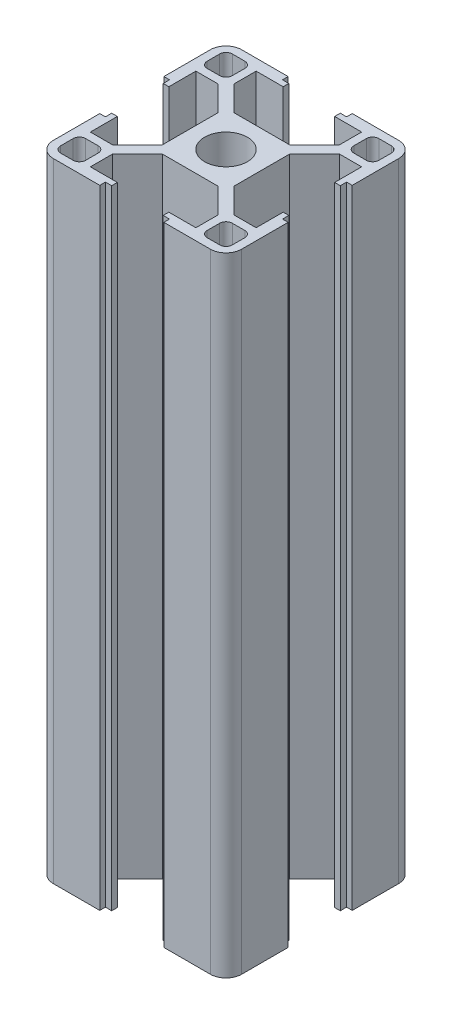
SolidWorks part; units mm, degrees
ref_plane "Front Plane" through (0, 0, 0) normal (0, 0, 1) x (1, 0, 0)
ref_plane "Top Plane" through (0, 0, 0) normal (0, 1, 0) x (1, 0, 0)
ref_plane "Right Plane" through (0, 0, 0) normal (1, 0, 0) x (0, 0, -1)
sketch "Sketch1" plane through (0, 0, 0) normal (0, 1, 0) x (1, 0, 0)
  line L0 (13.2, 8.4) -> (13.2, -8.4)
  line L1 (-12.5, -15) -> (12.5, -15)
  line L2 (-15, -12.5) -> (-15, 12.5)
  line L3 (-12.5, 15) -> (12.5, 15)
  line L4 (15, -12.5) -> (15, 12.5)
  line L5 (-15, -15) -> (15, 15) construction
  line L6 (-15, 15) -> (15, -15) construction
  line L7 (-4.4272, -5.7) -> (4.4272, -5.7)
  line L8 (-5.7, -4.4272) -> (-5.7, 4.4272)
  line L9 (-4.4272, 5.7) -> (4.4272, 5.7)
  line L10 (5.7, -4.4272) -> (5.7, 4.4272)
  line L11 (-5.7, -5.7) -> (5.7, 5.7) construction
  line L12 (-5.7, 5.7) -> (5.7, -5.7) construction
  line L13 (8.4, -13.2) -> (-8.4, -13.2)
  line L14 (-13.2, -8.4) -> (-13.2, 8.4)
  line L15 (-8.4, 13.2) -> (8.4, 13.2)
  line L16 (8.4, 13.2) -> (8.4, 9.6728)
  line L17 (8.4, 9.6728) -> (4.4272, 5.7)
  line L18 (9.6728, 8.4) -> (5.7, 4.4272)
  line L19 (13.2, 8.4) -> (9.6728, 8.4)
  line L20 (9.6728, -8.4) -> (5.5438, -4.271)
  line L21 (13.2, -8.4) -> (9.6728, -8.4)
  line L22 (8.4, -9.6728) -> (4.4272, -5.7)
  line L23 (8.4, -13.2) -> (8.4, -9.6728)
  line L24 (-8.4, -9.6728) -> (-4.4272, -5.7)
  line L25 (-8.4, -13.2) -> (-8.4, -9.6728)
  line L26 (-9.6728, -8.4) -> (-5.7, -4.4272)
  line L27 (-13.2, -8.4) -> (-9.6728, -8.4)
  line L28 (-9.6728, 8.4) -> (-5.7, 4.4272)
  line L29 (-13.2, 8.4) -> (-9.6728, 8.4)
  line L30 (-8.4, 9.6728) -> (-4.4272, 5.7)
  line L31 (-8.4, 13.2) -> (-8.4, 9.6728)
  line L32 (10.6728, 9.6728) -> (12.6728, 9.6728)
  line L33 (-12.6728, 9.6728) -> (-10.6728, 9.6728)
  line L34 (-13.6728, 10.6728) -> (-13.6728, 12.6728)
  line L35 (-12.6728, 13.6728) -> (-10.6728, 13.6728)
  line L36 (-9.6728, 10.6728) -> (-9.6728, 12.6728)
  line L37 (-13.6728, 9.6728) -> (-9.6728, 13.6728) construction
  line L38 (-13.6728, 13.6728) -> (-9.6728, 9.6728) construction
  line L39 (9.6728, 12.6728) -> (9.6728, 10.6728)
  line L40 (10.6728, 13.6728) -> (12.6728, 13.6728)
  line L41 (13.6728, 12.6728) -> (13.6728, 10.6728)
  line L42 (9.6728, -10.6728) -> (9.6728, -12.6728)
  line L43 (12.6728, -9.6728) -> (10.6728, -9.6728)
  line L44 (13.6728, -10.6728) -> (13.6728, -12.6728)
  line L45 (12.6728, -13.6728) -> (10.6728, -13.6728)
  line L46 (-10.6728, -9.6728) -> (-12.6728, -9.6728)
  line L47 (-9.6728, -12.6728) -> (-9.6728, -10.6728)
  line L48 (-10.6728, -13.6728) -> (-12.6728, -13.6728)
  line L49 (-13.6728, -12.6728) -> (-13.6728, -10.6728)
  arc A0 (-12.5, 15) -> (-15, 12.5) centre (-12.5, 12.5) ccw
  arc A1 (-12.5, -15) -> (-15, -12.5) centre (-12.5, -12.5) cw
  arc A2 (15, -12.5) -> (12.5, -15) centre (12.5, -12.5) cw
  arc A3 (15, 12.5) -> (12.5, 15) centre (12.5, 12.5) ccw
  arc A4 (-12.6728, 9.6728) -> (-13.6728, 10.6728) centre (-12.6728, 10.6728) cw
  arc A5 (-10.6728, 9.6728) -> (-9.6728, 10.6728) centre (-10.6728, 10.6728) ccw
  arc A6 (-9.6728, 12.6728) -> (-10.6728, 13.6728) centre (-10.6728, 12.6728) ccw
  arc A7 (-13.6728, 12.6728) -> (-12.6728, 13.6728) centre (-12.6728, 12.6728) cw
  arc A8 (9.6728, 10.6728) -> (10.6728, 9.6728) centre (10.6728, 10.6728) ccw
  arc A9 (9.6728, 12.6728) -> (10.6728, 13.6728) centre (10.6728, 12.6728) cw
  arc A10 (12.6728, 13.6728) -> (13.6728, 12.6728) centre (12.6728, 12.6728) cw
  arc A11 (12.6728, 9.6728) -> (13.6728, 10.6728) centre (12.6728, 10.6728) ccw
  arc A12 (10.6728, -9.6728) -> (9.6728, -10.6728) centre (10.6728, -10.6728) ccw
  arc A13 (12.6728, -9.6728) -> (13.6728, -10.6728) centre (12.6728, -10.6728) cw
  arc A14 (13.6728, -12.6728) -> (12.6728, -13.6728) centre (12.6728, -12.6728) cw
  arc A15 (9.6728, -12.6728) -> (10.6728, -13.6728) centre (10.6728, -12.6728) ccw
  arc A16 (-9.6728, -10.6728) -> (-10.6728, -9.6728) centre (-10.6728, -10.6728) ccw
  arc A17 (-9.6728, -12.6728) -> (-10.6728, -13.6728) centre (-10.6728, -12.6728) cw
  arc A18 (-12.6728, -13.6728) -> (-13.6728, -12.6728) centre (-12.6728, -12.6728) cw
  arc A19 (-12.6728, -9.6728) -> (-13.6728, -10.6728) centre (-12.6728, -10.6728) ccw
  circle A20 centre (0, 0) radius 3.4
  point P0 (0, 0)
  point P18 (0, 0)
  point P25 (13.2, 0)
  point P29 (0, 0)
  point P32 (0, 0)
  point P35 (0, 0)
  point P38 (0, 0)
  point P40 (-11.6728, 11.6728)
  point P61 (0, 0)
  point P109 (0, 0)
  dimension "D3" = 2.5
  dimension "D12" = 1
  dimension "D14" = 6.8
  dimension "D1" = 30
  dimension "D2" = 30
  dimension "D4" = 9.3
  dimension "D5" = 1.8
  dimension "D6" = 16.8
  dimension "D9" = 1.8
  dimension "D10" = 4
  dimension "D11" = 4
  dimension "D7" = 4
  dimension "D8" = 4
  dimension "D13" = 4
extrude "Boss-Extrude1" add sketch "Sketch1" along normal blind 100 contours L4 A3 L3 A0 L2 A1 L1 A2 A20 A19 L46 A16 L47 A17 L48 A18 L49 A15 L42 A12 L43 A13 L44 A14 L45 A11 L32 A8 L39 A9 L40 A10 L41 L14 L29 L28 L8 L26 L27 L13 L25 L24 L7 L22 L23 region at (-13.9678, 0, 13.9678)
sketch "Sketch2" plane through (0, 100, 0) normal (0, 1, 0) x (1, 0, 0)
  line L0 (-8.4, 13.2) -> (8.4, 13.2) construction
  line L1 (-8.4, 13.2) -> (8.4, 13.2)
  line L2 (0, 0) -> (0, 15) construction
  line L3 (-5.1, 15) -> (-5.1, 14.1)
  line L4 (15, -12.5) -> (15, 12.5)
  line L5 (12.5, 15) -> (-12.5, 15)
  line L6 (-15, 12.5) -> (-15, -12.5)
  line L7 (-12.5, -15) -> (12.5, -15)
  line L8 (15, -12.5) -> (15, 12.5)
  line L9 (12.5, 15) -> (-12.5, 15)
  line L10 (-15, 12.5) -> (-15, -12.5)
  line L11 (-12.5, -15) -> (12.5, -15)
  line L12 (-5.1, 14.1) -> (-4.1, 14.1)
  line L13 (-4.1, 14.1) -> (-4.1, 13.2)
  line L14 (4.1, 14.1) -> (4.1, 13.2)
  line L15 (5.1, 14.1) -> (4.1, 14.1)
  line L16 (5.1, 15) -> (5.1, 14.1)
  arc A4 (15, 12.5) -> (12.5, 15) centre (12.5, 12.5) ccw
  arc A5 (-12.5, 15) -> (-15, 12.5) centre (-12.5, 12.5) ccw
  arc A6 (-15, -12.5) -> (-12.5, -15) centre (-12.5, -12.5) ccw
  arc A7 (12.5, -15) -> (15, -12.5) centre (12.5, -12.5) ccw
  arc A8 (15, 12.5) -> (12.5, 15) centre (12.5, 12.5) ccw
  arc A9 (-12.5, 15) -> (-15, 12.5) centre (-12.5, 12.5) ccw
  arc A10 (-15, -12.5) -> (-12.5, -15) centre (-12.5, -12.5) ccw
  arc A11 (12.5, -15) -> (15, -12.5) centre (12.5, -12.5) ccw
  dimension "D2" = 4.1
  dimension "D3" = 5.1
  dimension "D4" = 0.9
  dimension "D1" = 0
extrude "Cut-Extrude1" cut sketch "Sketch2" against normal through all contours L2 L1 L14 L15 L16 L9 | L1 L2 L9 L3 L12 L13 region at (-2.3272, 100, -14.1489) region at (2.3272, 100, -14.1489)
ref_axis "Axis1" through (0, 105, 0) along (0, -1, 0)
pattern_circular "CirPattern1" count 4 over 360 about axis through (0, 105, 0) along (0, -1, 0) of "Cut-Extrude1"
